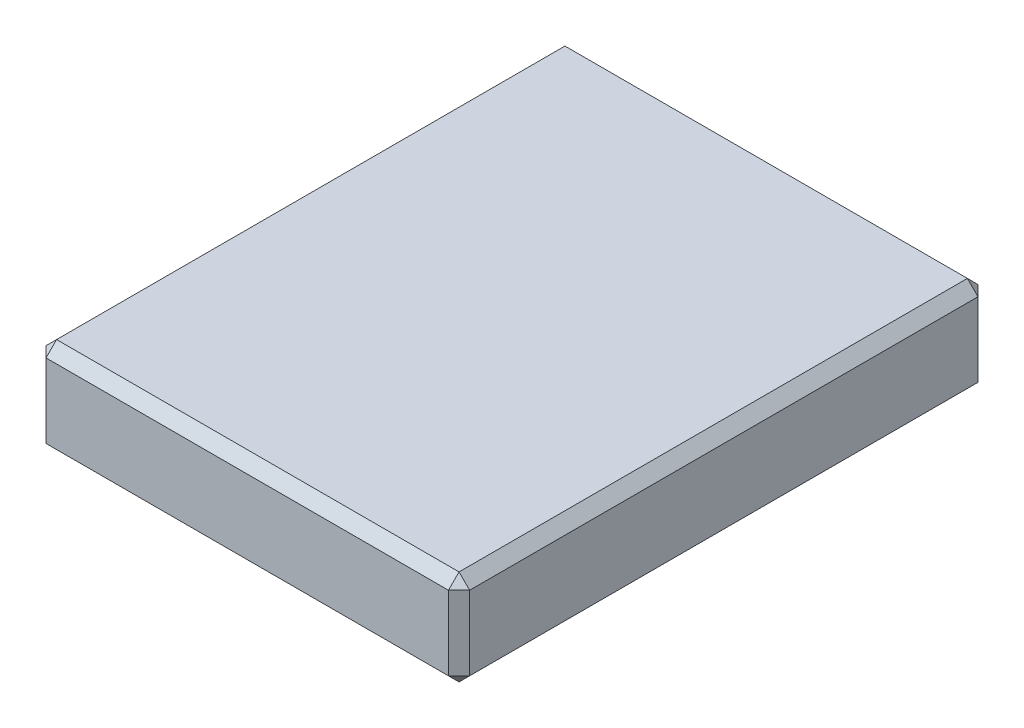
SolidWorks part; units mm, degrees
material "Acrylic (Medium-high impact)"
ref_plane "Front Plane" through (0, 0, 0) normal (0, 0, 1) x (1, 0, 0)
ref_plane "Top Plane" through (0, 0, 0) normal (0, 1, 0) x (1, 0, 0)
ref_plane "Right Plane" through (0, 0, 0) normal (1, 0, 0) x (0, 0, -1)
sketch "Sketch1" plane through (0, 0, 0) normal (0, 1, 0) x (1, 0, 0)
  line L0 (0, 0) -> (80, 0)
  line L1 (0, 0) -> (0, -100)
  line L2 (80, 0) -> (80, -100)
  line L3 (0, -100) -> (80, -100)
  dimension "D1" = 80
  dimension "D2" = 100
extrude "Boss-Extrude1" add sketch "Sketch1" along normal blind 18
chamfer "Chamfer1" distance 2 angle 45 12 edges at (40, 18, 0) (40, 0, 0) (40, 18, 100) (0, 9, 0) (0, 18, 50) (0, 9, 100) (0, 0, 50) (40, 0, 100) (80, 9, 100) (80, 18, 50) (80, 9, 0) (80, 0, 50)
